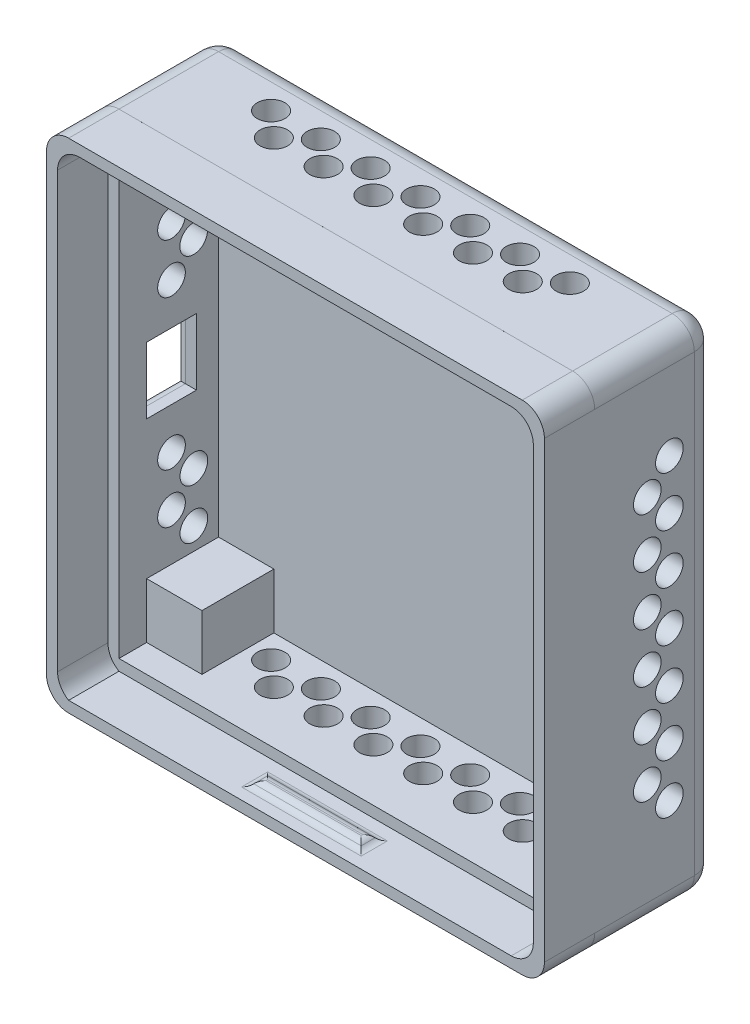
SolidWorks part; units mm, degrees
ref_plane "Piano frontale" through (0, 0, 0) normal (0, 0, 1) x (1, 0, 0)
ref_plane "Piano superiore" through (0, 0, 0) normal (0, 1, 0) x (1, 0, 0)
ref_plane "Piano destro" through (0, 0, 0) normal (1, 0, 0) x (0, 0, -1)
sketch "Schizzo2" plane through (0, 0, 0) normal (0, 0, 1) x (1, 0, 0)
  line L1 (0, 0) -> (45, 0)
  line L2 (0, 0) -> (0, 45)
  line L3 (0, 45) -> (45, 45)
  line L4 (45, 0) -> (45, 45)
  dimension "D1" = 45
  dimension "D2" = 45
extrude "Estrusione-Estrusione2" add sketch "Schizzo2" along normal blind 11
shell "Svuota1" thickness 2 removed face at (22.5, 22.5, 11)
fillet "Raccordo1" radius 2 4 edges at (45, 45, 5.5) (45, 0, 5.5) (0, 0, 5.5) (0, 45, 5.5)
fillet "Raccordo2" radius 2 8 edges at (44.4142, 0.5858, 0) (22.5, 0, 0) (0.5858, 0.5858, 0) (0, 22.5, 0) (0.5858, 44.4142, 0) (22.5, 45, 0) (44.4142, 44.4142, 0) (45, 22.5, 0)
sketch "Schizzo3" plane through (0, 0, 2) normal (0, 0, 1) x (1, 0, 0)
  line L0 (43, 43) -> (2, 43) construction
  line L1 (2, 43) -> (7, 43)
  line L2 (2, 43) -> (2, 38)
  line L3 (2, 38) -> (7, 38)
  line L4 (7, 43) -> (7, 38)
  line L5 (43, 43) -> (2, 43) construction
  dimension "D1" = 5
  dimension "D2" = 5
extrude "Estrusione-Estrusione3" add sketch "Schizzo3" along normal blind 6.5
sketch "Schizzo4" plane through (0, 0, 2) normal (0, 0, 1) x (1, 0, 0)
  line L1 (43, 2) -> (38, 2)
  line L2 (43, 2) -> (43, 7)
  line L3 (43, 7) -> (38, 7)
  line L4 (38, 2) -> (38, 7)
  dimension "D1" = 5
  dimension "D2" = 5
extrude "Estrusione-Estrusione4" add sketch "Schizzo4" along normal blind 6.5
fillet "Raccordo3" radius 4 2 edges at (38, 7, 5.25) (7, 38, 5.25)
sketch "Schizzo5" plane through (0, 0, 2) normal (0, 0, 1) x (1, 0, 0)
  line L0 (43, 2) -> (43, 43) construction
  line L1 (43, 43) -> (38, 43)
  line L2 (43, 43) -> (43, 38)
  line L3 (43, 38) -> (38, 38)
  line L4 (38, 43) -> (38, 38)
  line L5 (43, 43) -> (7, 43) construction
  line L7 (2, 2) -> (7, 2)
  line L8 (2, 2) -> (2, 7)
  line L9 (2, 7) -> (7, 7)
  line L10 (7, 2) -> (7, 7)
  dimension "D1" = 5
  dimension "D2" = 5
  dimension "D3" = 5
  dimension "D4" = 5
extrude "Estrusione-Estrusione5" add sketch "Schizzo5" along normal blind 6.5 contours L2 L1 L4 L3 | L8 L7 L10 L9
sketch "Schizzo12" plane through (0, 0, 11) normal (0, 0, 1) x (1, 0, 0)
  line L1 (0, 44.9999) -> (45, 44.9999)
  line L2 (0, 44.9999) -> (0, 43.9999)
  line L3 (0, 43.9999) -> (45, 43.9999)
  line L4 (45, 44.9999) -> (45, 43.9999)
  dimension "D1" = 45
  dimension "D2" = 1
extrude "Estrusione-Estrusione7" add sketch "Schizzo12" along normal blind 4.55
sketch "Schizzo13" plane through (0, 0, 11) normal (0, 0, 1) x (1, 0, 0)
  line L1 (45, 43.9999) -> (44, 43.9999)
  line L2 (45, 43.9999) -> (45, -0.0001)
  line L3 (45, -0.0001) -> (44, -0.0001)
  line L4 (44, 43.9999) -> (44, -0.0001)
  dimension "D1" = 44
  dimension "D2" = 1
extrude "Estrusione-Estrusione10" add sketch "Schizzo13" along normal blind 4.55
sketch "Schizzo15" plane through (0, 0, 11) normal (0, 0, 1) x (1, 0, 0)
  line L1 (44, -0.0001) -> (2, -0.0001)
  line L2 (44, -0.0001) -> (44, 0.9999)
  line L3 (44, 0.9999) -> (2, 0.9999)
  line L4 (2, -0.0001) -> (2, 0.9999)
  dimension "D1" = 1
  dimension "D2" = 42
extrude "Estrusione-Estrusione11" add sketch "Schizzo15" along normal blind 4.55
fillet "Raccordo4" radius 2 1 edges at (45, -0.0001, 13.275)
fillet "Raccordo5" radius 2 1 edges at (45, 44.9999, 13.275)
sketch "Schizzo17" plane through (0, 0, 11) normal (0, 0, 1) x (1, 0, 0)
  line L1 (0, 43.9999) -> (1, 43.9999)
  line L2 (0, 43.9999) -> (0, -0.0001)
  line L3 (0, -0.0001) -> (1, -0.0001)
  line L4 (1, 43.9999) -> (1, -0.0001)
  dimension "D1" = 1
  dimension "D2" = 44
extrude "Estrusione-Estrusione13" add sketch "Schizzo17" along normal blind 4.55
fillet "Raccordo6" radius 2 1 edges at (0, 44.9999, 13.275)
fillet "Raccordo7" radius 2 1 edges at (44, 0.9999, 13.275)
fillet "Raccordo8" radius 2 1 edges at (44, 43.9999, 13.275)
fillet "Raccordo9" radius 2 1 edges at (1, 43.9999, 13.275)
sketch "Schizzo18" plane through (0, 0, 11) normal (0, 0, 1) x (1, 0, 0)
  line L0 (1, -0.0001) -> (1, 41.9999) construction
  line L1 (2, -0.0001) -> (1, -0.0001)
  line L2 (2, -0.0001) -> (2, 0.9995)
  line L3 (2, 0.9995) -> (1, 0.9995)
  line L4 (1, -0.0001) -> (1, 0.9995)
extrude "Estrusione-Estrusione14" add sketch "Schizzo18" along normal blind 4.55
fillet "Raccordo10" radius 2 1 edges at (0, -0.0001, 13.275)
fillet "Raccordo11" radius 2 1 edges at (1, 0.9995, 13.275)
sketch "Schizzo22" plane through (0, 0.9999, 0) normal (0, 1, 0) x (1, 0, 0)
  line L5 (17.0049, -12.5647) -> (27.0049, -12.5647)
  line L6 (17.0049, -12.5647) -> (17.0049, -14.1147)
  line L7 (17.0049, -14.1147) -> (27.0049, -14.1147)
  line L8 (27.0049, -12.5647) -> (27.0049, -14.1147)
  dimension "D1" = 1.55
  dimension "D2" = 10
extrude "Estrusione-Estrusione15" add sketch "Schizzo22" along normal blind 0.5
fillet "Raccordo17" radius 0.74 4 edges at (27.0049, 1.4999, 13.3397) (22.0049, 1.4999, 12.5647) (17.0049, 1.4999, 13.3397) (22.0049, 1.4999, 14.1147)
fillet "Raccordo18" radius 0.74 4 edges at (22.0049, 0.9999, 12.5647) (27.0049, 0.9999, 13.3397) (17.0049, 0.9999, 13.3397) (22.0049, 0.9999, 14.1147)
sketch "Schizzo30" plane through (0, 43.9999, 0) normal (0, -1, 0) x (1, 0, 0)
  line L1 (17.0049, 14.1147) -> (27.0049, 14.1147)
  line L2 (17.0049, 14.1147) -> (17.0049, 12.5647)
  line L3 (17.0049, 12.5647) -> (27.0049, 12.5647)
  line L4 (27.0049, 14.1147) -> (27.0049, 12.5647)
extrude "Estrusione-Estrusione20" add sketch "Schizzo30" along normal blind 0.5 draft 1
fillet "Raccordo19" radius 0.74 4 edges at (22.0049, 43.4999, 12.5735) (26.9962, 43.4999, 13.3397) (22.0049, 43.4999, 14.106) (17.0136, 43.4999, 13.3397)
fillet "Raccordo20" radius 0.74 4 edges at (17.0049, 43.9999, 13.3397) (22.0049, 43.9999, 12.5647) (27.0049, 43.9999, 13.3397) (22.0049, 43.9999, 14.1147)
sketch "Schizzo34" plane through (43, 0, 0) normal (-1, 0, 0) x (0, 0, 1)
  circle A0 centre (4.2516, 35.9994) radius 1.25
  circle A1 centre (4.2516, 31.5034) radius 1.25
  circle A2 centre (4.2516, 27.0032) radius 1.25
  circle A3 centre (4.2516, 22.5053) radius 1.25
  circle A4 centre (4.2516, 18.0015) radius 1.25
  circle A5 centre (4.2516, 13.5036) radius 1.25
  circle A6 centre (4.2516, 9.0038) radius 1.25
  point P19 (2.7113, 7)
  dimension "D1" = 2.5
  dimension "D2" = 2.5
  dimension "D3" = 2.5
  dimension "D4" = 2.5
  dimension "D5" = 2.5
  dimension "D6" = 2.5
  dimension "D7" = 2.5
extrude "Taglio-Estrusione7" cut sketch "Schizzo34" against normal blind 2
sketch "Schizzo35" plane through (43, 0, 0) normal (-1, 0, 0) x (0, 0, 1)
  circle A0 centre (6.2524, 33.7503) radius 1.25
  circle A1 centre (6.2524, 29.2487) radius 1.25
  circle A2 centre (6.2524, 24.7505) radius 1.25
  circle A3 centre (6.2524, 20.2517) radius 1.25
  circle A4 centre (6.2524, 15.7547) radius 1.25
  circle A5 centre (6.2524, 11.252) radius 1.25
  dimension "D1" = 2.5
  dimension "D2" = 2.5
  dimension "D3" = 2.5
  dimension "D4" = 2.5
  dimension "D5" = 2.5
  dimension "D6" = 2.5
extrude "Taglio-Estrusione8" cut sketch "Schizzo35" against normal blind 2
sketch "Schizzo36" plane through (0, 2, 0) normal (0, 1, 0) x (1, 0, 0)
  circle A0 centre (35.9868, -4.2536) radius 1.25
  circle A1 centre (31.4911, -4.2536) radius 1.25
  circle A2 centre (26.996, -4.2536) radius 1.25
  circle A3 centre (22.4971, -4.2536) radius 1.25
  circle A4 centre (17.9983, -4.2536) radius 1.25
  circle A5 centre (13.4999, -4.2536) radius 1.25
  circle A6 centre (9.0039, -4.2536) radius 1.25
  dimension "D1" = 2.5
  dimension "D2" = 2.5
  dimension "D3" = 2.5
  dimension "D4" = 2.5
  dimension "D5" = 2.5
  dimension "D6" = 2.5
  dimension "D7" = 2.5
extrude "Taglio-Estrusione9" cut sketch "Schizzo36" against normal blind 2
sketch "Schizzo37" plane through (0, 2, 0) normal (0, 1, 0) x (1, 0, 0)
  circle A0 centre (33.7463, -6.2534) radius 1.25
  circle A1 centre (29.2472, -6.2534) radius 1.25
  circle A2 centre (24.7485, -6.2534) radius 1.25
  circle A3 centre (20.2458, -6.2534) radius 1.25
  circle A4 centre (15.749, -6.2534) radius 1.25
  circle A5 centre (11.2492, -6.2534) radius 1.25
  point P17 (7, -3.2646)
  dimension "D1" = 2.5
  dimension "D2" = 2.5
  dimension "D3" = 2.5
  dimension "D4" = 2.5
  dimension "D5" = 2.5
  dimension "D6" = 2.5
extrude "Taglio-Estrusione10" cut sketch "Schizzo37" against normal blind 2
sketch "Schizzo38" plane through (0, 43, 0) normal (0, -1, 0) x (-1, 0, 0)
  circle A0 centre (-8.9935, -4.2481) radius 1.25
  circle A1 centre (-13.4899, -4.2481) radius 1.25
  circle A2 centre (-17.9905, -4.2481) radius 1.25
  circle A3 centre (-22.4934, -4.2481) radius 1.25
  circle A4 centre (-26.9933, -4.2481) radius 1.25
  circle A5 centre (-31.495, -4.2481) radius 1.25
  circle A6 centre (-35.9965, -4.2481) radius 1.25
  dimension "D1" = 2.5
  dimension "D2" = 2.5
  dimension "D3" = 2.5
  dimension "D4" = 2.5
  dimension "D5" = 2.5
  dimension "D6" = 2.5
  dimension "D7" = 2.5
extrude "Taglio-Estrusione11" cut sketch "Schizzo38" against normal blind 2
sketch "Schizzo39" plane through (0, 43, 0) normal (0, -1, 0) x (-1, 0, 0)
  circle A0 centre (-11.2508, -6.2534) radius 1.25
  circle A1 centre (-15.7484, -6.2534) radius 1.25
  circle A2 centre (-20.2458, -6.2534) radius 1.25
  circle A3 centre (-24.7485, -6.2534) radius 1.25
  circle A4 centre (-29.2472, -6.2534) radius 1.25
  circle A5 centre (-33.7463, -6.2534) radius 1.25
  dimension "D1" = 2.5
  dimension "D2" = 2.5
  dimension "D3" = 2.5
  dimension "D4" = 2.5
  dimension "D5" = 2.5
  dimension "D6" = 2.5
extrude "Taglio-Estrusione12" cut sketch "Schizzo39" against normal blind 2
sketch "Schizzo40" plane through (2, 0, 0) normal (1, 0, 0) x (0, 0, -1)
  circle A0 centre (-4.2347, 8.9988) radius 1.25
  circle A1 centre (-4.2347, 13.4961) radius 1.25
  circle A2 centre (-4.2527, 35.9982) radius 1.25
  circle A3 centre (-4.2527, 31.4945) radius 1.25
  dimension "D1" = 2.5
  dimension "D2" = 2.5
  dimension "D5" = 2.5
  dimension "D6" = 2.5
sketch "Schizzo42" plane through (2, 0, 0) normal (1, 0, 0) x (0, 0, -1)
  line L0 (-8.5, 25.5052) -> (-4, 25.5052)
  line L5 (-8.5, 25.5052) -> (-8.5, 19.5052)
  line L6 (-8.5, 19.5052) -> (-4, 19.5052)
  line L7 (-4, 25.5052) -> (-4, 19.5052)
  dimension "D1" = 6
  dimension "D2" = 4.5
extrude "Taglio-Estrusione13" cut sketch "Schizzo42" against normal blind 2
fillet "Raccordo21" radius 1 4 edges at (0, 19.5052, 6.25) (0, 22.5052, 4) (0, 25.5052, 6.25) (0, 22.5052, 8.5)
extrude "Taglio-Estrusione14" cut sketch "Schizzo40" against normal blind 2
sketch "Schizzo43" plane through (2, 0, 0) normal (1, 0, 0) x (0, 0, -1)
  circle A0 centre (-6.2524, 11.2507) radius 1.25
  circle A1 centre (-6.2524, 15.7515) radius 1.25
  circle A2 centre (-6.2524, 29.2485) radius 1.25
  circle A3 centre (-6.2524, 33.7503) radius 1.25
  dimension "D1" = 2.5
  dimension "D2" = 2.5
  dimension "D3" = 2.5
  dimension "D4" = 2.5
extrude "Taglio-Estrusione15" cut sketch "Schizzo43" against normal blind 2
